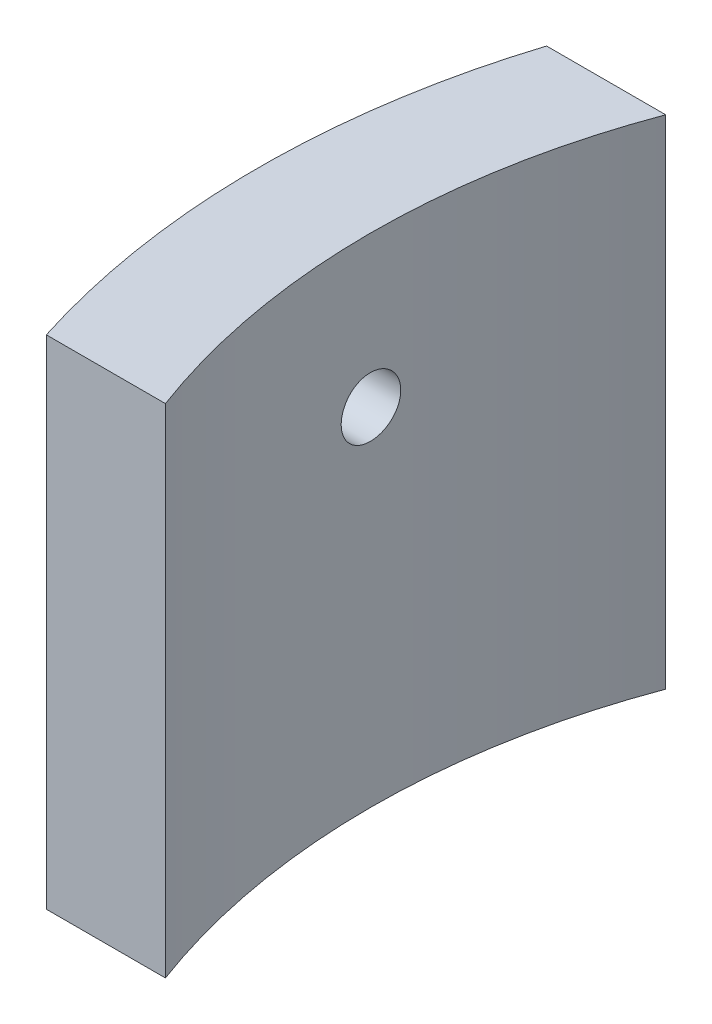
SolidWorks part; units mm, degrees
material "ABS"
ref_plane "Front Plane" through (0, 0, 0) normal (0, 0, 1) x (1, 0, 0)
ref_plane "Top Plane" through (0, 0, 0) normal (0, 1, 0) x (1, 0, 0)
ref_plane "Right Plane" through (0, 0, 0) normal (1, 0, 0) x (0, 0, -1)
sketch "Sketch1" plane through (0, 0, 0) normal (0, 1, 0) x (1, 0, 0)
  line L0 (-42.0402, -13.335) -> (-35.6902, -13.335)
  line L1 (-42.0402, 13.335) -> (-35.6902, 13.335)
  line L2 (-35.6902, 13.335) -> (0, 0) construction
  line L3 (0, 0) -> (-35.6902, -13.335) construction
  line L4 (-88.519, 13.335) -> (-35.6902, 13.335) construction
  arc A0 (-35.6902, 13.335) -> (-35.6902, -13.335) centre (0, 0) ccw
  arc A1 (-42.0402, 13.335) -> (-42.0402, -13.335) centre (0, 0) ccw
  dimension "D1" = 38.1
  dimension "D2" = 6.35
extrude "Boss-Extrude1" add sketch "Sketch1" along normal blind 38.1
ref_plane "Plane1" through (-42.0402, 0, 0) normal (-1, 0, 0) x (0, 0, 1)
sketch "Sketch2" plane through (-42.0402, 0, 0) normal (-1, 0, 0) x (0, 0, 1)
  line L0 (0, 38.1) -> (0, 0) construction
  line L1 (13.335, 38.1) -> (-13.335, 38.1) construction
  circle A0 centre (0, 30.0704) radius 1.5875
  circle A1 centre (0, 30.0704) radius 4.7625
  circle A2 centre (0, 30.0704) radius 1.5875 construction
  dimension "D1" = 3.175
extrude "Boss-Extrude3" add sketch "Sketch2" along normal up to surface (2.4098 mm away)
ref_plane "Plane2" through (-44.1044, 0, 0) normal (-1, 0, 0) x (0, 0, 1)
ref_plane "Plane3" through (-50.4544, 0, 0) normal (-1, 0, 0) x (0, 0, 1)
sketch "Sketch3" plane through (0, 0, 0) normal (0, -1, 0) x (1, 0, 0)
  line L0 (-42.0402, 13.335) -> (-35.6902, 13.335)
  line L1 (-42.0402, -13.335) -> (-35.6902, -13.335)
  arc A0 (-42.0402, 13.335) -> (-42.0402, -13.335) centre (0, 0) ccw
  arc A1 (-35.6902, -13.335) -> (-35.6902, 13.335) centre (0, 0) cw
  arc A2 (-42.0402, 13.335) -> (-42.0402, -13.335) centre (0, 0) ccw construction
  arc A3 (-35.6902, 13.335) -> (-35.6902, -13.335) centre (0, 0) ccw construction
extrude "Cut-Extrude1" cut sketch "Sketch3" against normal up to surface (11.5792 mm away)
sketch "Sketch5" plane through (-44.45, 0, 0) normal (-1, 0, 0) x (0, 0, 1)
  circle A0 centre (0, 30.0704) radius 1.5875
  circle A1 centre (0, 30.0704) radius 1.5875 construction
extrude "Cut-Extrude4" cut sketch "Sketch5" against normal through all
